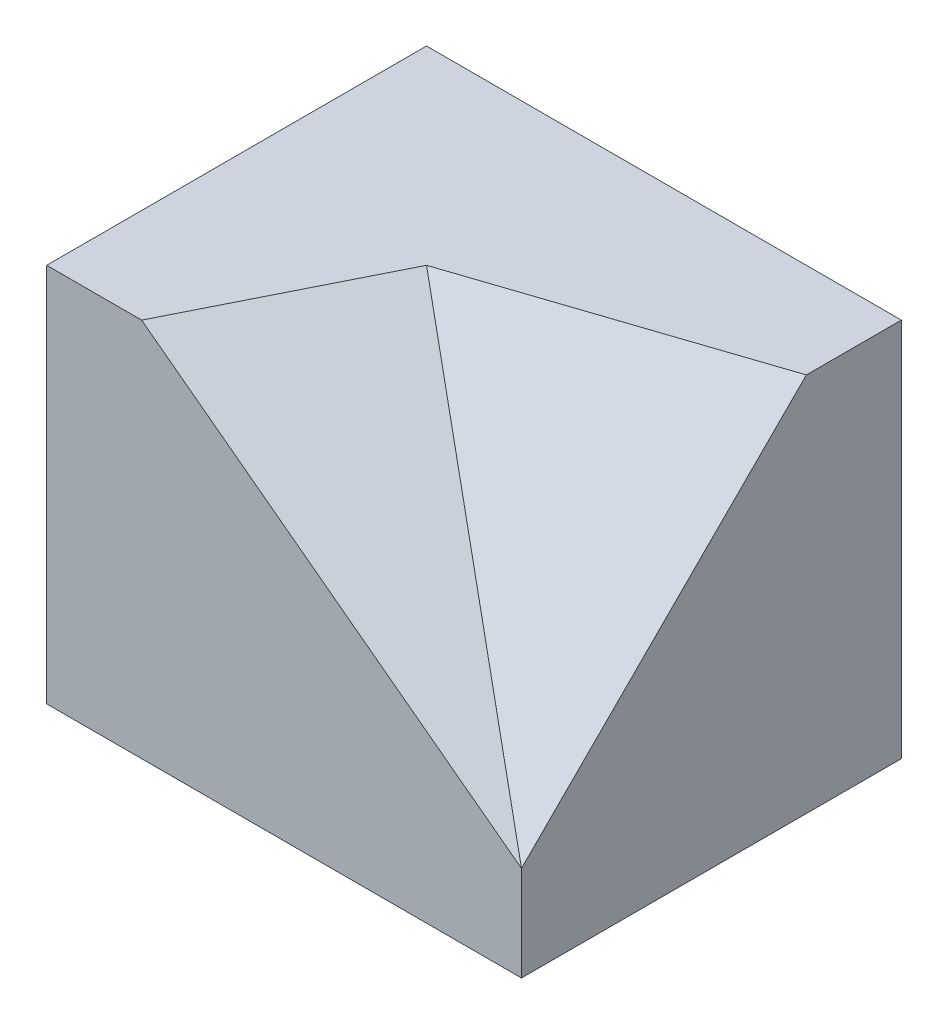
SolidWorks part; units mm, degrees
ref_plane "前基準面" through (0, 0, 0) normal (0, 0, 1) x (1, 0, 0)
ref_plane "上基準面" through (0, 0, 0) normal (0, 1, 0) x (1, 0, 0)
ref_plane "右基準面" through (0, 0, 0) normal (1, 0, 0) x (0, 0, -1)
sketch "草圖1" plane through (0, 0, 0) normal (0, 0, 1) x (1, 0, 0)
  line L1 (0, 0) -> (-50, 0)
  line L2 (0, 0) -> (0, -40)
  line L3 (0, -40) -> (-50, -40)
  line L4 (-50, 0) -> (-50, -40)
  dimension "D1" = 40
  dimension "D2" = 50
extrude "填料-伸長1" add sketch "草圖1" along normal blind 40
sketch "草圖2" plane through (0, 0, 0) normal (0, 1, 0) x (1, 0, 0)
  line L0 (0, -10) -> (-30, -20)
  line L1 (0, -40) -> (0, 0) construction
  line L2 (-30, -20) -> (0, -40)
  line L3 (0, -40) -> (0, -10)
  line L4 (0, -40) -> (-50, -40) construction
  point P9 (0.3073, -39.9021)
  dimension "D1" = 10
  dimension "D2" = 30
  dimension "D3" = 20
sketch "草圖3" plane through (0, 0, 40) normal (0, 0, 1) x (1, 0, 0)
  point P7 (0, -30)
loft "除料-疊層拉伸1" cut profiles "草圖3", "草圖2"
sketch "草圖4" plane through (0, 0, 0) normal (0, 1, 0) x (1, 0, 0)
  line L0 (-30, -20) -> (-40, -40)
  line L1 (0, -40) -> (-50, -40) construction
  line L2 (-40, -40) -> (0, -40)
  line L3 (0, -40) -> (-30, -20)
  line L4 (-50, -40) -> (-50, 0) construction
  dimension "D1" = 10
loft "除料-疊層拉伸2" cut profiles "草圖4", "草圖3<2>"
sketch "草圖3<2>" plane through (0, 0, 40) normal (0, 0, 1) x (1, 0, 0) same geometry as "草圖3"
